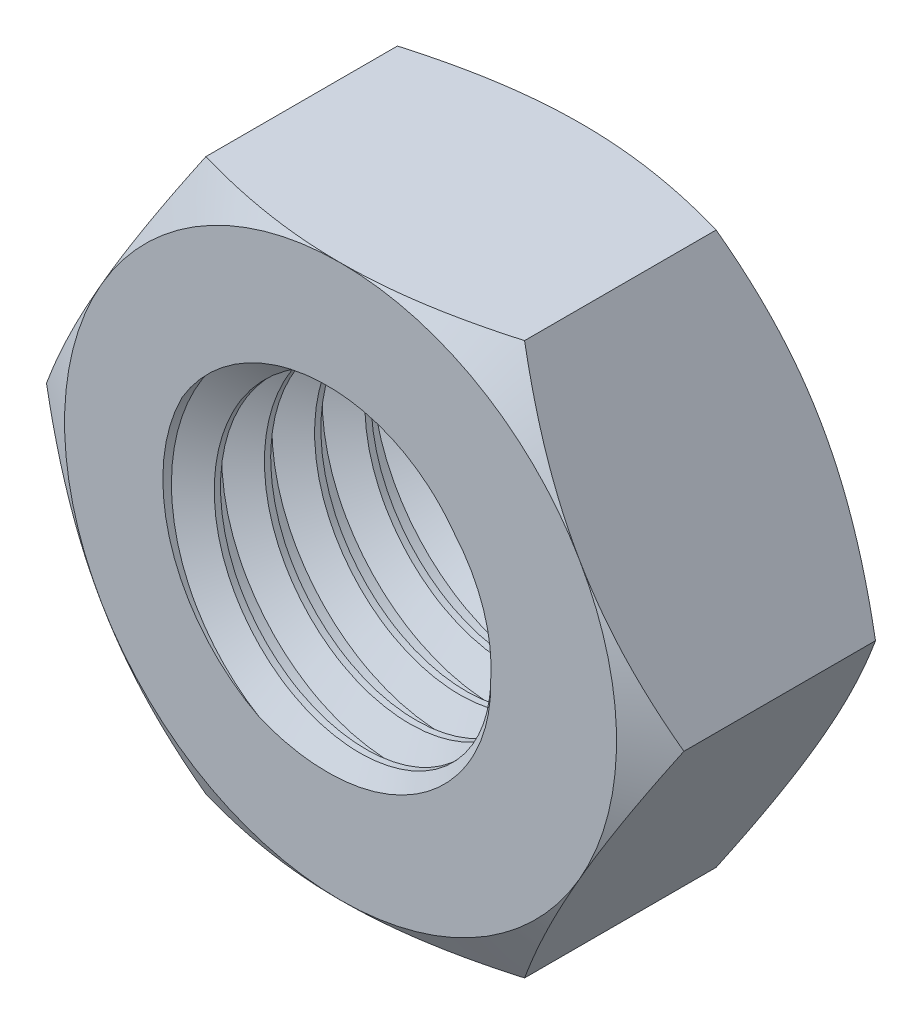
SolidWorks part; units mm, degrees
ref_plane "前视基准面" through (0, 0, 0) normal (0, 0, 1) x (1, 0, 0)
ref_plane "上视基准面" through (0, 0, 0) normal (0, 1, 0) x (1, 0, 0)
ref_plane "右视基准面" through (0, 0, 0) normal (1, 0, 0) x (0, 0, -1)
sketch "草图1" plane through (0, 0, 0) normal (0, 0, 1) x (1, 0, 0)
  line L1 (3.1754, 0) -> (1.5877, 2.75)
  line L2 (1.5877, 2.75) -> (-1.5877, 2.75)
  line L3 (-1.5877, 2.75) -> (-3.1754, 0)
  line L4 (-3.1754, 0) -> (-1.5877, -2.75)
  line L5 (-1.5877, -2.75) -> (1.5877, -2.75)
  line L6 (1.5877, -2.75) -> (3.1754, 0)
  circle A0 centre (0, 0) radius 2.75 construction
  dimension "D1" = 5.5
extrude "拉伸1" add sketch "草图1" along normal blind 2.4
sketch "草图2" plane through (0, 0, 0) normal (0, 0, -1) x (-1, 0, 0)
  circle A0 centre (0, 0) radius 2.75
  dimension "D1" = 5.5
sketch "草图3" plane through (0, 0, 0) normal (0, 1, 0) x (1, 0, 0)
  line L0 (2.75, 0) -> (3.1754, -0.2456)
  line L1 (2.75, 0) -> (-2.75, 0)
  line L2 (2.75, 0) -> (-2.75, 0)
  line L3 (3.1754, -2.4) -> (3.1754, 0) construction
  line L4 (2.75, 0) -> (3.1754, 0)
  line L5 (3.1754, 0) -> (3.1754, -0.2456)
  line L6 (0, 4.959) -> (0, -21.1771) construction
  dimension "D2" = 30
  dimension "D1" = 0
revolve "切除-旋转1" cut sketch "草图3" angle 360 about L6
sketch "草图4" plane through (0, 0, 2.4) normal (0, 0, 1) x (1, 0, 0)
  circle A0 centre (0, 0) radius 2.75
  dimension "D1" = 5.5
sketch "草图5" plane through (0, 0, 0) normal (0, 1, 0) x (1, 0, 0)
  line L0 (2.75, -2.4) -> (3.1754, -2.1544)
  line L1 (-2.75, -2.4) -> (2.75, -2.4)
  line L2 (-2.75, -2.4) -> (2.75, -2.4)
  line L3 (3.1754, -2.4) -> (3.1754, -0.2456) construction
  line L4 (2.75, -2.4) -> (3.1754, -2.4)
  line L5 (3.1754, -2.1544) -> (3.1754, -2.4)
  line L6 (0, 5.5944) -> (0, -24.6427) construction
  dimension "D2" = 30
  dimension "D1" = 0
revolve "切除-旋转2" cut sketch "草图5" angle 360 about L6
sketch "草图6" plane through (0, 0, 2.4) normal (0, 0, 1) x (1, 0, 0)
  circle A0 centre (0, 0) radius 1.5
  dimension "D1" = 3
extrude "切除-拉伸1" cut sketch "草图6" against normal through all
sketch "草图7" plane through (0, 0, 0) normal (1, 0, 0) x (0, 0, -1)
  line L0 (-4.9903, -1.5) -> (2.3037, -1.5) construction
  line L1 (-2.4, -1.5) -> (0, -1.5) construction
  line L2 (0, -11.5678) -> (0, -23.4371) construction
  line L3 (0, -2.75) -> (0, -1.375) construction
  line L4 (0, -1.375) -> (0, 1.375) construction
  line L5 (-0.0625, -1.7706) -> (-0.2188, -1.5)
  line L6 (0.0625, -1.7706) -> (0.2188, -1.5)
  line L7 (-0.2188, -1.5) -> (0.2188, -1.5)
  line L8 (-0.0625, -1.7706) -> (0.0625, -1.7706)
  dimension "D1" = 30
  dimension "D2" = 30
  dimension "D3" = 0.4375
  dimension "D4" = 0.125
sketch "草图8" plane through (0, 0, 0) normal (0, 0, -1) x (-1, 0, 0)
  circle A0 centre (0, 0) radius 1.5
  dimension "D1" = 3
curve "螺旋线1" pitch 0.5 height 2.4 turns 4.8
sweep "切除-扫描1" cut profiles "草图7" path "螺旋线1"
